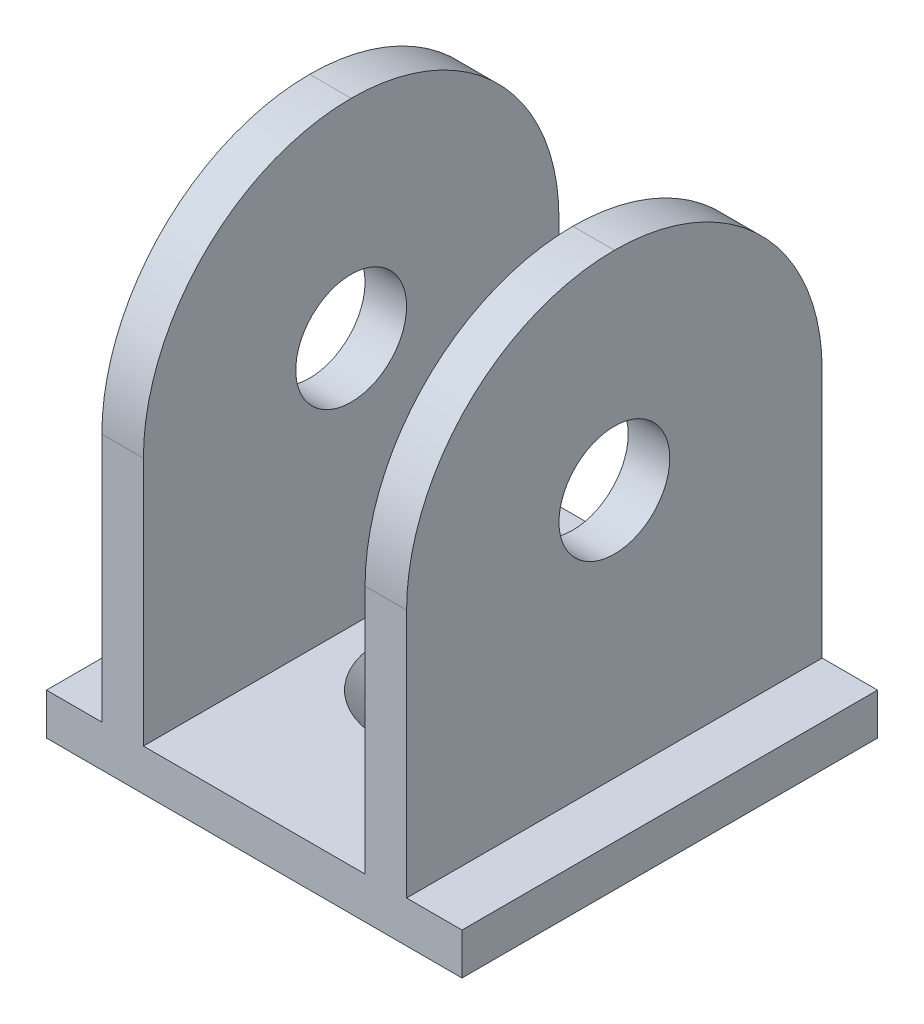
SolidWorks part; units mm, degrees
ref_plane "Alzado" through (0, 0, 0) normal (0, 0, 1) x (1, 0, 0)
ref_plane "Planta" through (0, 0, 0) normal (0, 1, 0) x (1, 0, 0)
ref_plane "Vista lateral" through (0, 0, 0) normal (1, 0, 0) x (0, 0, -1)
sketch "Croquis1" plane through (0, 0, 0) normal (0, 1, 0) x (1, 0, 0)
  line L1 (15, -15) -> (-15, -15)
  line L2 (15, -15) -> (15, 15)
  line L3 (15, 15) -> (-15, 15)
  line L4 (-15, -15) -> (-15, 15)
  line L5 (15, -15) -> (-15, 15) construction
  line L6 (15, 15) -> (-15, -15) construction
  point P0 (0, 0)
  dimension "D1" = 30
  dimension "D2" = 30
extrude "Saliente-Extruir1" add sketch "Croquis1" along normal blind 3
sketch "Croquis2" plane through (0, 3, 0) normal (0, 1, 0) x (1, 0, 0)
  line L0 (15, 15) -> (-15, 15) construction
  line L1 (-11, 15) -> (-8, 15)
  line L2 (-11, 15) -> (-11, -15)
  line L3 (-11, -15) -> (-8, -15)
  line L4 (-8, 15) -> (-8, -15)
  line L5 (-15, -15) -> (15, -15) construction
  line L6 (-15, 8.9544) -> (-11, 8.9544) construction
  line L7 (11, 15) -> (8, 15)
  line L8 (11, 15) -> (11, -15)
  line L9 (11, -15) -> (8, -15)
  line L10 (8, 15) -> (8, -15)
  line L11 (-15, 15) -> (-15, -15) construction
  line L12 (11, -11.3045) -> (15, -11.3045) construction
  line L13 (15, -15) -> (15, 15) construction
  dimension "D1" = 3
  dimension "D2" = 3
  dimension "D3" = 4
extrude "Saliente-Extruir2" add sketch "Croquis2" along normal blind 33
fillet "Redondeo1" radius 15 4 edges at (-9.5, 36, -15) (9.5, 36, -15) (9.5, 36, 15) (-9.5, 36, 15)
sketch "Croquis3" plane through (11, 0, 0) normal (1, 0, 0) x (0, 0, -1)
  circle A0 centre (0, 21) radius 4
  dimension "D1" = 8
extrude "Cortar-Extruir1" cut sketch "Croquis3" against normal through all
sketch "Croquis4" plane through (0, 3, 0) normal (0, 1, 0) x (1, 0, 0)
  circle A0 centre (0, 0) radius 3
  dimension "D1" = 6
extrude "Cortar-Extruir2" cut sketch "Croquis4" against normal through all
chamfer "Chaflán1" distance 3 angle 45 1 edges at (0, 3, 3)
